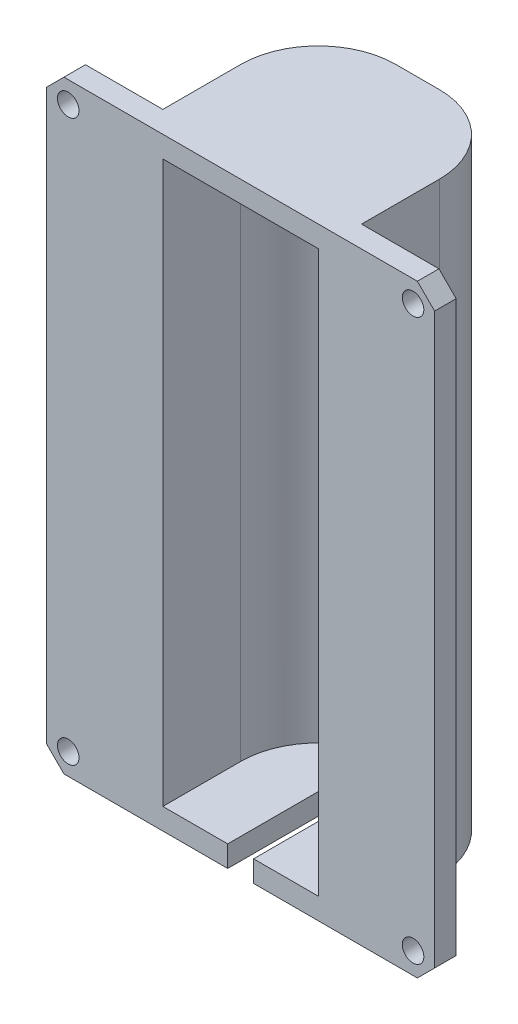
SolidWorks part; units mm, degrees
ref_plane "Front Plane" through (0, 0, 0) normal (0, 0, 1) x (1, 0, 0)
ref_plane "Top Plane" through (0, 0, 0) normal (0, 1, 0) x (1, 0, 0)
ref_plane "Right Plane" through (0, 0, 0) normal (1, 0, 0) x (0, 0, -1)
sketch "Sketch1" plane through (0, 0, 0) normal (0, 0, 1) x (1, 0, 0)
  line L0 (22.5, -35) -> (22.5, 35)
  line L1 (-9.025, -32.525) -> (9.025, -32.525)
  line L2 (-9.025, -32.525) -> (-9.025, 32.525)
  line L3 (-9.025, 32.525) -> (9.025, 32.525)
  line L4 (9.025, -32.525) -> (9.025, 32.525)
  line L5 (-9.025, -32.525) -> (9.025, 32.525) construction
  line L6 (-9.025, 32.525) -> (9.025, -32.525) construction
  line L7 (-22.5, 35) -> (22.5, 35)
  line L8 (-22.5, -35) -> (-22.5, 35)
  line L9 (-22.5, -35) -> (22.5, -35)
  line L10 (0, -35) -> (0, -21.525) construction
  line L11 (-1.5, -32.525) -> (-1.5, -35)
  line L12 (1.5, -32.525) -> (1.5, -35)
  line L13 (-20, -32.5) -> (-20, 32.5) construction
  line L14 (-20, 32.5) -> (20, 32.5) construction
  line L15 (20, -32.5) -> (20, 32.5) construction
  line L16 (-20, -32.5) -> (20, -32.5) construction
  line L17 (0, 32.525) -> (0, 35) construction
  line L18 (9.025, 0) -> (22.5, 0) construction
  line L19 (-9.025, 0) -> (-22.5, 0) construction
  point P0 (0, 0)
  dimension "D1" = 40
  dimension "D2" = 65
  dimension "D4" = 3
  dimension "D3" = 18.05
  dimension "D5" = 65.05
  dimension "D6" = 70
  dimension "D7" = 45
  dimension "D8" = 5
  dimension "D9" = 2.5
  dimension "D10" = 2.475
extrude "Boss-Extrude1" add sketch "Sketch1" along normal blind 18.03 contours L1 L12 L9 L0 L7 L8 L11 L2 L3 L4 region at (12, -34.1678, 0)
extrude "Boss-Extrude2" add sketch "Sketch1<3>" against normal blind 5.5 contours L1 L12 L9 L0 L7 L8 L11 L2 L3 L4 | L1 L4 L3 L2 | L12 L1 L11 L9 region at (12, -34.1678, 0) region at (0, -33.7625, 0) region at (0, 0, 0)
sketch "Sketch1<3>" plane through (0, 0, 0) normal (0, 0, 1) x (1, 0, 0) same geometry as "Sketch1"
fillet "Fillet1" radius 9 2 edges at (-9.025, 0, 0) (9.025, 0, 0)
sketch "Sketch4" plane through (0, -35, 0) normal (0, -1, 0) x (1, 0, 0)
  line L0 (-22.5, 18.03) -> (-22.5, -5.5) construction
  line L1 (-22.5, 15.53) -> (-11.525, 15.53)
  line L2 (-22.5, 15.53) -> (-22.5, -5.5)
  line L3 (-22.5, -5.5) -> (-11.525, -5.5)
  line L4 (-11.525, 15.53) -> (-11.525, -5.5)
  line L5 (0, 0) -> (0, 18.03) construction
  line L6 (-9.025, 18.03) -> (9.025, 18.03) construction
  line L7 (-9.025, 18.03) -> (-9.025, 9) construction
  line L8 (11.525, -2.5) -> (-11.525, -2.5)
  line L9 (0, -2.5) -> (0, -5.5)
  line L10 (11.525, -5.5) -> (-11.525, -5.5)
  line L11 (-11.525, -2.5) -> (-11.525, -5.5)
  line L12 (-22.5, 18.03) -> (-1.5, 18.03) construction
  line L13 (-22.5, -5.5) -> (22.5, -5.5) construction
  line L14 (11.525, -2.5) -> (11.525, -5.5)
  line L15 (22.5, -5.5) -> (11.525, -5.5)
  line L16 (11.525, 15.53) -> (11.525, -5.5)
  line L17 (22.5, 15.53) -> (11.525, 15.53)
  line L18 (22.5, 15.53) -> (22.5, -5.5)
  line M14 (-22.5, 18.03) -> (-22.5, -5.5)
  line M15 (-22.5, -5.5) -> (22.5, -5.5)
  line M16 (22.5, -5.5) -> (22.5, 18.03)
  dimension "D1" = 2.5
  dimension "D2" = 2.5
  dimension "D3" = 2.5
extrude "Cut-Extrude1" cut sketch "Sketch4" against normal blind 103 contours L14 L8 L9 M15 | L17 L16 L14 M16 M15 | L9 L8 L4 M15 | L4 L1 M14 M15 region at (-17.0125, -35, 5.015) region at (-5.7625, -35, -4) region at (5.7625, -35, -4) region at (17.0125, -35, 5.015)
sketch "Sketch2" plane through (0, 0, -5.5) normal (0, 0, -1) x (-1, 0, 0)
  point P0 (20, 32.5)
  point P3 (-20, 32.5)
  point P6 (-20, -32.5)
  point P9 (20, -32.5)
  point P12 (-20, 32.5)
  point P14 (20, 32.5)
  point P16 (20, -32.5)
  point P18 (-20, -32.5)
  point P22 (-20, 32.5)
  point P24 (20, 32.5)
  point P26 (-20, 32.5)
  point P28 (20, 32.5)
  point P30 (20, -32.5)
  point P32 (-20, -32.5)
hole_wizard "Tap Drill for M3 Tap1" positions "Sketch2" profile "Sketch3" hole size "M3" standard "ISO" end condition through all
sketch "Sketch3" plane through (-20, 32.5, -5.5) normal (1, 0, 0) x (0, 1, 0)
  line L0 (0, 0) -> (0, 23.53)
  line L1 (0, 23.53) -> (1.25, 23.53)
  line L2 (1.25, 23.53) -> (1.25, 0.025)
  line L3 (1.25, 0.025) -> (1.275, 0)
  line L5 (1.275, 0) -> (0, 0)
  line L6 (-1.25, 0.025) -> (-1.275, 0) construction
  line L11 (0, -6.35) -> (0, 107.95) construction
  dimension "Thru Hole Dia." = 2.5
  dimension "Thru Hole Depth" = 23.53
  dimension "Near C'Sink Dia." = 2.55
  dimension "Near C'Sink Angle" = 90
chamfer "Chamfer1" distance 2 angle 45 4 edges at (22.5, -35, 16.78) (22.5, 35, 16.78) (-22.5, 35, 16.78) (-22.5, -35, 16.78)
fillet "Fillet2" radius 9 2 edges at (-11.525, 0, -2.5) (11.525, 0, -2.5)
